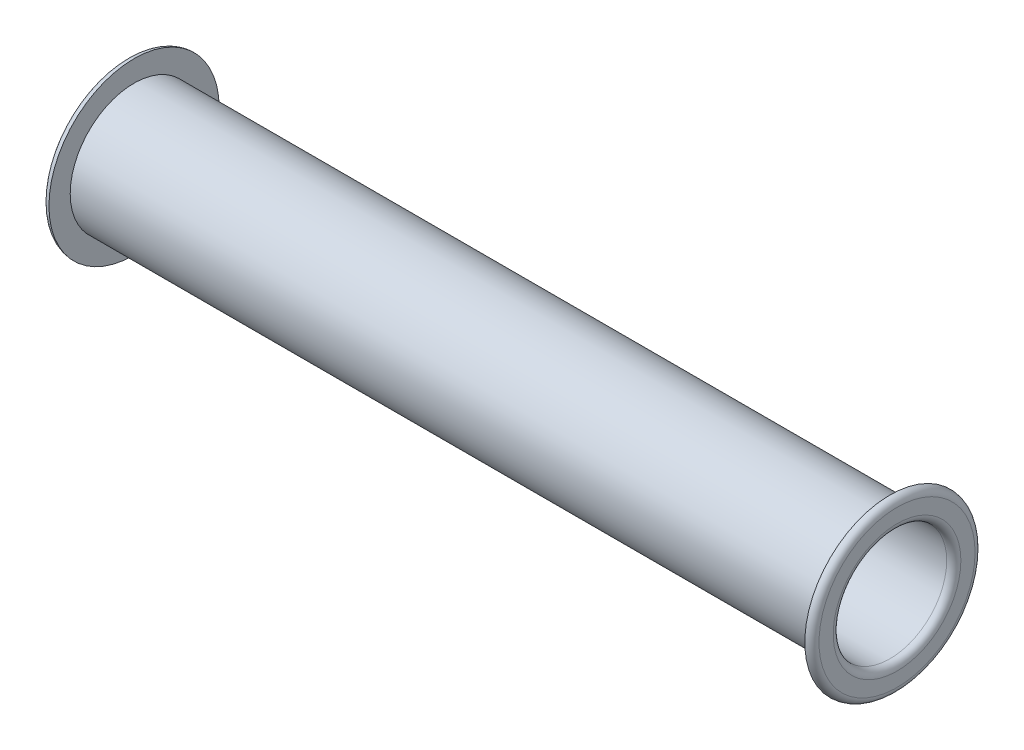
SolidWorks part; units mm, degrees
material "Chrome Stainless Steel"
ref_plane "Front" through (0, 0, 0) normal (0, 0, 1) x (1, 0, 0)
ref_plane "Top" through (0, 0, 0) normal (0, 1, 0) x (1, 0, 0)
ref_plane "Right" through (0, 0, 0) normal (1, 0, 0) x (0, 0, -1)
sketch "Sketch1" plane through (0, 0, 0) normal (1, 0, 0) x (0, 0, -1)
  circle A0 centre (0, 0) radius 2.286
  dimension "D1" = 4.572
extrude "Extrude1" add sketch "Sketch1" along normal mid plane 27.0637
sketch "Sketch2" plane through (13.5318, 0, 0) normal (1, 0, 0) x (0, 0, -1)
  circle A2 centre (0, 0) radius 3.048
  circle A3 centre (0, 0) radius 3.048
  dimension "D1" = 0.762
extrude "Extrude2" add sketch "Sketch2" along normal blind 0.254
fillet "Fillet1" radius 0.254 1 edges at (13.7858, 0, -3.048)
mirror "Mirror1" about plane through (0, 0, 0) normal (1, 0, 0) of "Extrude2", "Fillet1"
sketch "Sketch3" plane through (13.7858, 0, 0) normal (1, 0, 0) x (0, 0, -1)
  circle A0 centre (0, 0) radius 2.032
  dimension "D1" = 4.064
extrude "Cut-Extrude1" cut sketch "Sketch3" against normal through all
fillet "Fillet2" radius 0.254 2 edges at (-13.7858, 0, -2.032) (13.7858, 0, -2.032)
